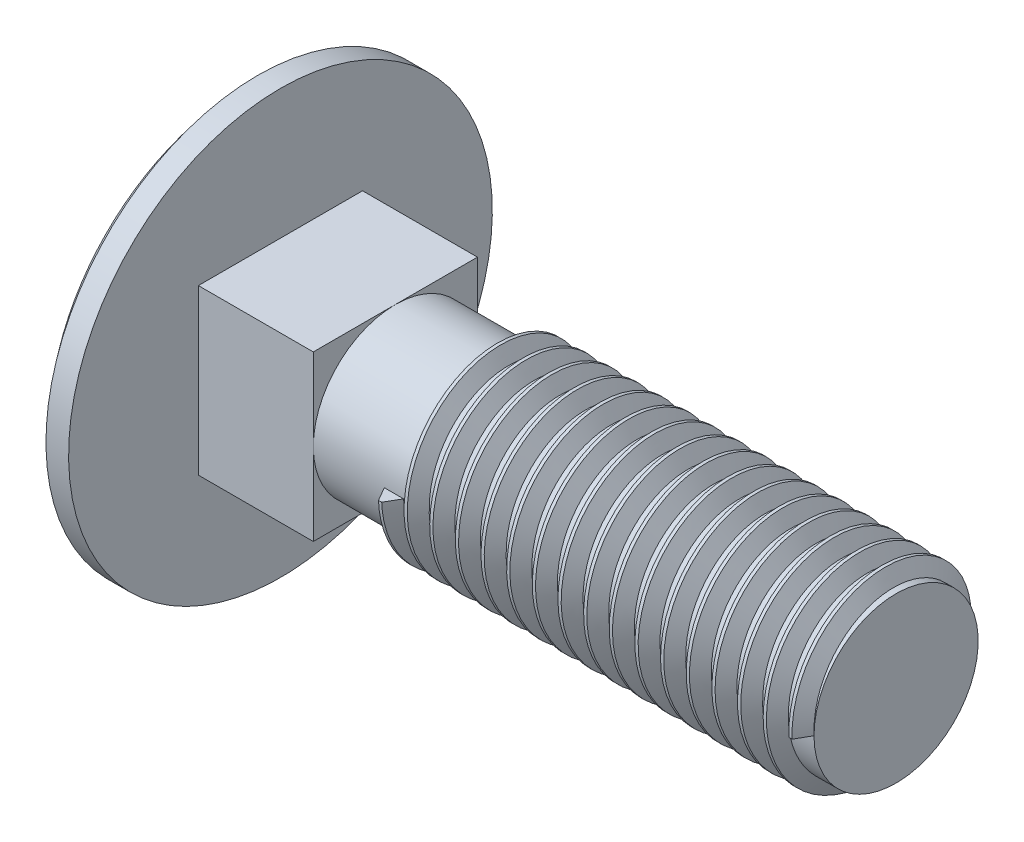
SolidWorks part; units mm, degrees
ref_plane "Спереди" through (0, 0, 0) normal (0, 0, 1) x (1, 0, 0)
ref_plane "Сверху" through (0, 0, 0) normal (0, 1, 0) x (1, 0, 0)
ref_plane "Справа" through (0, 0, 0) normal (1, 0, 0) x (0, 0, -1)
sketch "Эскиз1" plane through (0, 0, 0) normal (0, 0, 1) x (1, 0, 0)
  line L0 (0, 0) -> (0, 10.325)
  line L1 (0, 10.325) -> (-1.1027, 10.325)
  line L2 (0, 0) -> (-4.88, 0)
  arc A0 (-1.1027, 10.325) -> (-4.88, 0) centre (11.12, 0) ccw
  point P7 (-9.3709, 0)
  point P8 (-5.2418, 0)
  point P9 (-6.1704, 0)
  point P10 (0, 0)
  dimension "D1" = 16
  dimension "D2" = 10.325
  dimension "D3" = 4.88
revolve "Шляпка" add sketch "Эскиз1" angle 360 about L2
sketch "Эскиз2" plane through (0, 0, 0) normal (1, 0, 0) x (0, 0, -1)
  line L1 (-4, 4) -> (4, 4)
  line L2 (-4, 4) -> (-4, -4)
  line L3 (-4, -4) -> (4, -4)
  line L4 (4, 4) -> (4, -4)
  line L5 (-4, 4) -> (4, -4) construction
  line L6 (-4, -4) -> (4, 4) construction
  point P0 (0, 0)
  dimension "D1" = 8
extrude "Подголовник" add sketch "Эскиз2" along normal blind 5.6
sketch "Эскиз3" plane through (0, 0, 0) normal (0, 1, 0) x (1, 0, 0)
  line L0 (5.6, 0) -> (30, 0)
  line L1 (5.6, 4) -> (5.6, -4) construction
  line L2 (30, 0) -> (30, 4)
  line L3 (30, 4) -> (5.6, 4)
  line L4 (5.6, 4) -> (5.6, 0)
  line L5 (0, -10.325) -> (0, 10.325) construction
  dimension "D1" = 4
  dimension "D2" = 30
revolve "Резьбовая часть" add sketch "Эскиз3" angle 360 about L0
thread "Резьба1" pitch 1.25 method extrude profile "Профиль резьбы1" start angle 0, offset 0, length 20, pitch 1.25, diameter 8
ref_plane "Плоскость1" through (30, 0, 4) normal (0, -1, 0) x (0, 0, 1)
sketch "Профиль резьбы1" plane through (30, 0, 4) normal (0, -1, 0) x (0, 0, 1)
  line L0 (0, 0) -> (0, 1.25) construction
  line L1 (0, 0) -> (0.6766, 0.3906)
  line L2 (0.6766, 0.3906) -> (0.6766, 0.5469)
  line L3 (0.6766, 0.5469) -> (0, 0.9375)
  line L4 (0.6766, 0.4687) -> (0, 0.4687) construction
  line L11 (0, 0) -> (0, 0.9375)
  point P2 (0, 0)
  dimension "Pitch" = 1.25
  dimension "Profile_Angle" = 60
  dimension "Profile_Land" = 0.1562
  dimension "Profile_Height" = 0.6766
